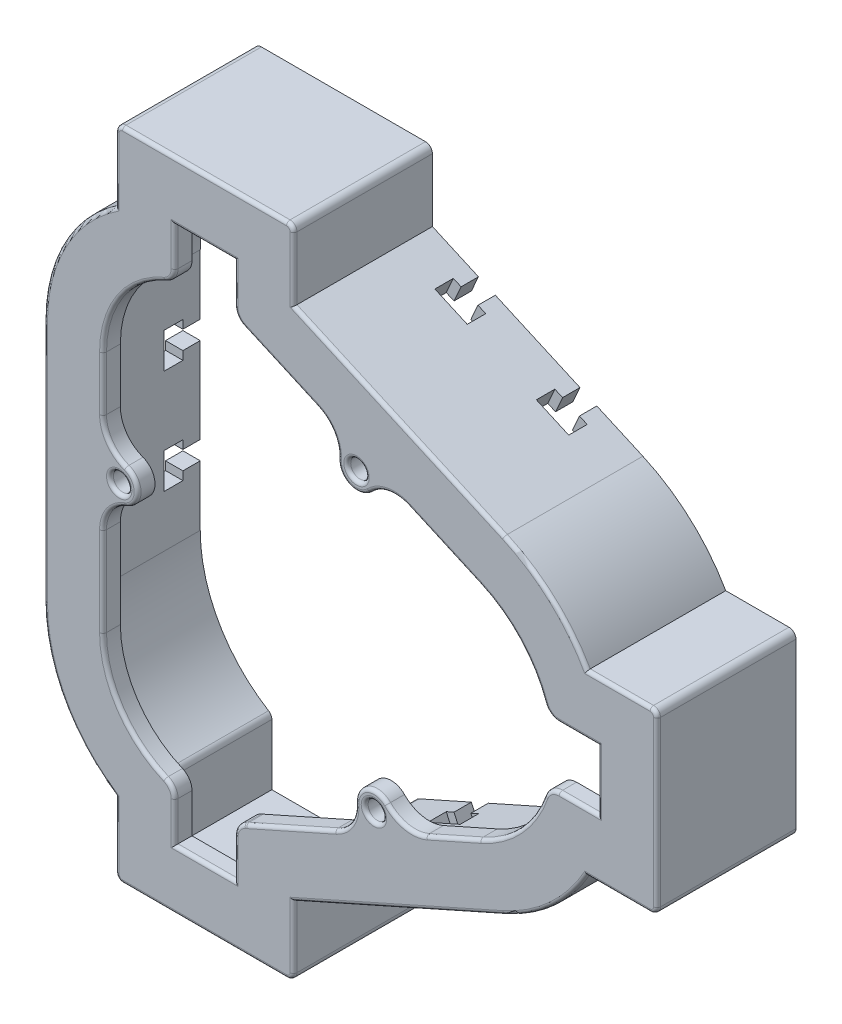
SolidWorks part; units mm, degrees
ref_plane "Front Plane" through (0, 0, 0) normal (0, 0, 1) x (1, 0, 0)
ref_plane "Top Plane" through (0, 0, 0) normal (0, 1, 0) x (1, 0, 0)
ref_plane "Right Plane" through (0, 0, 0) normal (1, 0, 0) x (0, 0, -1)
sketch "Sketch1" plane through (0, 0, -80.01) normal (0, 0, -1) x (-1, 0, 0)
  line L0 (14.1705, 137.7093) -> (22.108, 137.7093) construction
  line L1 (-128.3273, 40.8549) -> (-128.3273, 32.9174) construction
  line L2 (14.1705, -63.937) -> (22.108, -63.937) construction
  line L3 (55.2868, -7.5638) -> (55.2868, 81.3362)
  line L4 (29.093, 120.8247) -> (29.093, 135.1693)
  line L5 (29.093, 135.1693) -> (22.108, 135.1693)
  line L6 (14.1705, 135.1693) -> (22.108, 135.1693)
  line L7 (14.1705, 135.1693) -> (7.1855, 135.1693)
  line L8 (7.1855, 135.1693) -> (7.1855, 120.8247)
  line L9 (3.0278, 115.2711) -> (-82.5915, 77.144)
  line L10 (-111.5749, 47.8399) -> (-125.7873, 47.8399)
  line L11 (-125.7873, 47.8399) -> (-125.7873, 40.8549)
  line L12 (-125.7873, 40.8549) -> (-125.7873, 32.9174)
  line L13 (-125.7873, 32.9174) -> (-125.7873, 25.9324)
  line L14 (-125.7873, 25.9324) -> (-111.5749, 25.9324)
  line L15 (-82.5915, -3.3716) -> (3.0278, -41.4987)
  line L16 (7.1855, -47.0524) -> (7.1855, -61.397)
  line L17 (7.1855, -61.397) -> (14.1705, -61.397)
  line L18 (14.1705, -61.397) -> (22.108, -61.397)
  line L19 (22.108, -61.397) -> (29.093, -61.397)
  line L20 (29.093, -61.397) -> (29.093, -47.0524)
  line L21 (57.8268, -7.5638) -> (57.8268, 81.3362)
  line L22 (31.633, 120.8247) -> (31.633, 137.7093)
  line L23 (31.633, 137.7093) -> (22.108, 137.7093)
  line L24 (22.108, 137.7093) -> (22.108, 117.6323)
  line L25 (14.1705, 117.6323) -> (14.1705, 137.7093)
  line L26 (14.1705, 137.7093) -> (4.6455, 137.7093)
  line L27 (4.6455, 137.7093) -> (4.6455, 120.8247)
  line L28 (1.9945, 117.5914) -> (-83.6248, 79.4643)
  line L29 (-111.5749, 50.3799) -> (-128.3273, 50.3799)
  line L30 (-128.3273, 50.3799) -> (-128.3273, 40.8549)
  line L31 (-128.3273, 40.8549) -> (-106.0032, 40.8549)
  line L32 (-106.0032, 32.9174) -> (-128.3273, 32.9174)
  line L33 (-128.3273, 32.9174) -> (-128.3273, 23.3924)
  line L34 (-128.3273, 23.3924) -> (-111.5749, 23.3924)
  line L35 (-83.6248, -5.692) -> (1.9945, -43.8191)
  line L36 (4.6455, -47.0524) -> (4.6455, -63.937)
  line L37 (4.6455, -63.937) -> (14.1705, -63.937)
  line L38 (14.1705, -63.937) -> (14.1705, -43.86)
  line L39 (22.108, -43.86) -> (22.108, -63.937)
  line L40 (22.108, -63.937) -> (31.633, -63.937)
  line L41 (31.633, -63.937) -> (31.633, -47.0524)
  line L42 (57.8268, -7.5638) -> (57.8268, 81.3362) construction
  line L43 (31.633, 120.8247) -> (31.633, 137.7093) construction
  line L44 (31.633, 137.7093) -> (22.108, 137.7093) construction
  line L47 (14.1705, 137.7093) -> (4.6455, 137.7093) construction
  line L48 (4.6455, 137.7093) -> (4.6455, 120.8247) construction
  line L49 (1.9945, 117.5914) -> (-83.6248, 79.4643) construction
  line L50 (-111.5749, 50.3799) -> (-128.3273, 50.3799) construction
  line L51 (-128.3273, 50.3799) -> (-128.3273, 40.8549) construction
  line L54 (-128.3273, 32.9174) -> (-128.3273, 23.3924) construction
  line L55 (-128.3273, 23.3924) -> (-111.5749, 23.3924) construction
  line L56 (-83.6248, -5.692) -> (1.9945, -43.8191) construction
  line L57 (4.6455, -47.0524) -> (4.6455, -63.937) construction
  line L58 (4.6455, -63.937) -> (14.1705, -63.937) construction
  line L61 (22.108, -63.937) -> (31.633, -63.937) construction
  line L62 (31.633, -63.937) -> (31.633, -47.0524) construction
  line L63 (76.8768, -7.5638) -> (76.8768, 81.3362)
  line L64 (50.683, 130.234) -> (50.683, 156.7593)
  line L65 (50.683, 156.7593) -> (22.108, 156.7593)
  line L66 (14.1705, 156.7593) -> (22.108, 156.7593)
  line L67 (14.1705, 156.7593) -> (-14.4045, 156.7593)
  line L68 (-14.4045, 156.7593) -> (-14.4045, 131.1423)
  line L69 (-14.4045, 131.1423) -> (-91.3743, 96.8669)
  line L70 (-121.6907, 69.4299) -> (-147.3773, 69.4299)
  line L71 (-147.3773, 69.4299) -> (-147.3773, 40.8549)
  line L72 (-147.3773, 40.8549) -> (-147.3773, 32.9174)
  line L73 (-147.3773, 32.9174) -> (-147.3773, 4.3424)
  line L74 (-147.3773, 4.3424) -> (-121.6907, 4.3424)
  line L75 (-91.3743, -23.0945) -> (-14.4045, -57.3699)
  line L76 (-14.4045, -57.3699) -> (-14.4045, -82.987)
  line L77 (-14.4045, -82.987) -> (14.1705, -82.987)
  line L78 (14.1705, -82.987) -> (22.108, -82.987)
  line L79 (22.108, -82.987) -> (50.683, -82.987)
  line L80 (50.683, -82.987) -> (50.683, -56.4617)
  line L81 (70.5268, -7.5638) -> (70.5268, 81.3362)
  line L82 (44.333, 126.7051) -> (44.333, 150.4093)
  line L83 (44.333, 150.4093) -> (22.108, 150.4093)
  line L84 (14.1705, 150.4093) -> (22.108, 150.4093)
  line L85 (14.1705, 150.4093) -> (-8.0545, 150.4093)
  line L86 (-8.0545, 150.4093) -> (-8.0545, 127.0188)
  line L87 (-8.0545, 127.0188) -> (-88.7911, 91.066)
  line L88 (-117.8756, 63.0799) -> (-141.0273, 63.0799)
  line L89 (-141.0273, 63.0799) -> (-141.0273, 40.8549)
  line L90 (-141.0273, 40.8549) -> (-141.0273, 32.9174)
  line L91 (-141.0273, 32.9174) -> (-141.0273, 10.6924)
  line L92 (-141.0273, 10.6924) -> (-117.8756, 10.6924)
  line L93 (-88.7911, -17.2937) -> (-8.0545, -53.2465)
  line L94 (-8.0545, -53.2465) -> (-8.0545, -76.637)
  line L95 (-8.0545, -76.637) -> (14.1705, -76.637)
  line L96 (14.1705, -76.637) -> (22.108, -76.637)
  line L97 (22.108, -76.637) -> (44.333, -76.637)
  line L98 (44.333, -76.637) -> (44.333, -52.9327)
  circle A3 centre (18.1393, 81.3362) radius 19.05 construction
  circle A4 centre (18.1393, -7.5638) radius 47.625 construction
  circle A5 centre (-58.3701, 37.7264) radius 19.05 construction
  arc A6 (-37.3265, 52.1691) -> (-96.2173, 33.5834) centre (-66.7719, 42.8762) ccw construction
  arc A7 (-37.3265, 52.1691) -> (-96.2173, 33.5834) centre (-66.7719, 42.8762) ccw construction
  arc A8 (-97.1709, 33.2824) -> (-36.3728, 52.4701) centre (-66.7719, 42.8762) ccw construction
  arc A9 (-97.1709, 33.2824) -> (-36.3728, 52.4701) centre (-66.7719, 42.8762) ccw construction
  circle A10 centre (18.1393, 81.3362) radius 36.5125 construction
  circle A11 centre (18.1393, 81.3362) radius 36.5125 construction
  circle A12 centre (49.3813, 43.2476) radius 3.3782
  circle A13 centre (-43.805, -14.1791) radius 3.3782
  circle A14 centre (-37.4305, 90.7903) radius 3.3782
  arc A15 (33.5733, -44.1273) -> (57.8268, -7.5638) centre (18.1393, -7.5638) ccw
  arc A16 (57.8268, 81.3362) -> (33.5733, 117.8997) centre (18.1393, 81.3362) ccw
  arc A17 (31.633, 120.8247) -> (33.5733, 117.8997) centre (34.808, 120.8247) ccw
  arc A18 (14.1705, 117.6323) -> (22.108, 117.6323) centre (18.1393, 81.3362) ccw
  arc A19 (2.7053, 117.8997) -> (4.6455, 120.8247) centre (1.4705, 120.8247) ccw
  arc A20 (2.7053, 117.8997) -> (1.9945, 117.5914) centre (18.1393, 81.3362) ccw
  arc A21 (-83.6248, 79.4643) -> (-108.5831, 52.4919) centre (-64.6643, 36.8862) ccw
  arc A22 (-111.5749, 50.3799) -> (-108.5831, 52.4919) centre (-111.5749, 53.5549) ccw
  arc A23 (-106.0032, 32.9174) -> (-106.0032, 40.8549) centre (-64.6643, 36.8862) ccw
  arc A24 (-108.5831, 21.2805) -> (-111.5749, 23.3924) centre (-111.5749, 20.2174) ccw
  arc A25 (-108.5831, 21.2805) -> (-83.6248, -5.692) centre (-64.6643, 36.8862) ccw
  arc A26 (1.9945, -43.8191) -> (2.7053, -44.1273) centre (18.1393, -7.5638) ccw
  arc A27 (4.6455, -47.0524) -> (2.7053, -44.1273) centre (1.4705, -47.0524) ccw
  arc A28 (22.108, -43.86) -> (14.1705, -43.86) centre (18.1393, -7.5638) ccw
  arc A29 (33.5733, -44.1273) -> (31.633, -47.0524) centre (34.808, -47.0524) ccw
  arc A30 (33.5733, -44.1273) -> (57.8268, -7.5638) centre (18.1393, -7.5638) ccw construction
  arc A31 (57.8268, 81.3362) -> (33.5733, 117.8997) centre (18.1393, 81.3362) ccw construction
  arc A32 (31.633, 120.8247) -> (33.5733, 117.8997) centre (34.808, 120.8247) ccw construction
  arc A34 (2.7053, 117.8997) -> (4.6455, 120.8247) centre (1.4705, 120.8247) ccw construction
  arc A35 (2.7053, 117.8997) -> (1.9945, 117.5914) centre (18.1393, 81.3362) ccw construction
  arc A36 (-83.6248, 79.4643) -> (-108.5831, 52.4919) centre (-64.6643, 36.8862) ccw construction
  arc A37 (-111.5749, 50.3799) -> (-108.5831, 52.4919) centre (-111.5749, 53.5549) ccw construction
  arc A39 (-108.5831, 21.2805) -> (-111.5749, 23.3924) centre (-111.5749, 20.2174) ccw construction
  arc A40 (-108.5831, 21.2805) -> (-83.6248, -5.692) centre (-64.6643, 36.8862) ccw construction
  arc A41 (1.9945, -43.8191) -> (2.7053, -44.1273) centre (18.1393, -7.5638) ccw construction
  arc A42 (4.6455, -47.0524) -> (2.7053, -44.1273) centre (1.4705, -47.0524) ccw construction
  arc A44 (33.5733, -44.1273) -> (31.633, -47.0524) centre (34.808, -47.0524) ccw construction
  arc A45 (-80.8179, 75.1448) -> (-76.0259, 76.8308) centre (-64.6643, 36.8862) ccw construction
  arc A46 (-80.8179, 75.1448) -> (-76.0259, 76.8308) centre (-64.6643, 36.8862) ccw construction
  circle A47 centre (-43.805, -14.1791) radius 6.7564
  circle A48 centre (49.3813, 43.2476) radius 6.7564
  circle A49 centre (-37.4305, 90.7903) radius 6.7564
  arc A50 (32.5855, -41.7872) -> (55.2868, -7.5638) centre (18.1393, -7.5638) ccw
  arc A51 (55.2868, 81.3362) -> (32.5855, 115.5596) centre (18.1393, 81.3362) ccw
  arc A52 (29.093, 120.8247) -> (32.5855, 115.5596) centre (34.808, 120.8247) ccw
  arc A53 (3.693, 115.5596) -> (7.1855, 120.8247) centre (1.4705, 120.8247) ccw
  arc A54 (3.693, 115.5596) -> (3.0278, 115.2711) centre (18.1393, 81.3362) ccw
  arc A55 (-82.5915, 77.144) -> (-106.1897, 51.6414) centre (-64.6643, 36.8862) ccw
  arc A56 (-111.5749, 47.8399) -> (-106.1897, 51.6414) centre (-111.5749, 53.5549) ccw
  arc A57 (-106.1897, 22.1309) -> (-111.5749, 25.9324) centre (-111.5749, 20.2174) ccw
  arc A58 (-106.1897, 22.1309) -> (-82.5915, -3.3716) centre (-64.6643, 36.8862) ccw
  arc A59 (3.0278, -41.4987) -> (3.693, -41.7872) centre (18.1393, -7.5638) ccw
  arc A60 (7.1855, -47.0524) -> (3.693, -41.7872) centre (1.4705, -47.0524) ccw
  arc A61 (32.5855, -41.7872) -> (29.093, -47.0524) centre (34.808, -47.0524) ccw
  arc A62 (50.683, -56.4617) -> (76.8768, -7.5638) centre (18.1393, -7.5638) ccw
  arc A63 (76.8768, 81.3362) -> (50.683, 130.234) centre (18.1393, 81.3362) ccw
  arc A64 (50.683, 130.234) -> (50.683, 130.234) centre (50.683, 130.234) ccw
  arc A65 (-14.4045, 131.1423) -> (-14.4045, 131.1423) centre (-14.4045, 131.1423) ccw
  arc A66 (-14.4045, 131.1423) -> (-14.4045, 131.1423) centre (-14.4045, 131.1423) cw
  arc A67 (-91.3743, 96.8669) -> (-121.6907, 69.4299) centre (-64.6643, 36.8862) ccw
  arc A68 (-121.6907, 69.4299) -> (-121.6907, 69.4299) centre (-121.6907, 69.4299) ccw
  arc A69 (-121.6907, 4.3424) -> (-121.6907, 4.3424) centre (-121.6907, 4.3424) ccw
  arc A70 (-121.6907, 4.3424) -> (-91.3743, -23.0945) centre (-64.6643, 36.8862) ccw
  arc A71 (-14.4045, -57.3699) -> (-14.4045, -57.3699) centre (-14.4045, -57.3699) cw
  arc A72 (-14.4045, -57.3699) -> (-14.4045, -57.3699) centre (-14.4045, -57.3699) ccw
  arc A73 (50.683, -56.4617) -> (50.683, -56.4617) centre (50.683, -56.4617) ccw
  arc A74 (44.333, -52.9327) -> (70.5268, -7.5638) centre (18.1393, -7.5638) ccw
  arc A75 (70.5268, 81.3362) -> (44.333, 126.7051) centre (18.1393, 81.3362) ccw
  arc A76 (44.333, 126.7051) -> (44.333, 126.7051) centre (44.333, 126.7051) ccw
  arc A77 (-8.0545, 127.0188) -> (-8.0545, 127.0188) centre (-8.0545, 127.0188) ccw
  arc A78 (-8.0545, 127.0188) -> (-8.0545, 127.0188) centre (-8.0545, 127.0188) cw
  arc A79 (-88.7911, 91.066) -> (-117.8756, 63.0799) centre (-64.6643, 36.8862) ccw
  arc A80 (-117.8756, 63.0799) -> (-117.8756, 63.0799) centre (-117.8756, 63.0799) ccw
  arc A81 (-117.8756, 10.6924) -> (-117.8756, 10.6924) centre (-117.8756, 10.6924) ccw
  arc A82 (-117.8756, 10.6924) -> (-88.7911, -17.2937) centre (-64.6643, 36.8862) ccw
  arc A83 (-8.0545, -53.2465) -> (-8.0545, -53.2465) centre (-8.0545, -53.2465) cw
  arc A84 (-8.0545, -53.2465) -> (-8.0545, -53.2465) centre (-8.0545, -53.2465) ccw
  arc A85 (44.333, -52.9327) -> (44.333, -52.9327) centre (44.333, -52.9327) ccw
  point P68 (-40.8151, 98.5279)
  arc M83 (33.5733, -44.1273) -> (57.8268, -7.5638) centre (18.1393, -7.5638) ccw
  line M84 (57.8268, -7.5638) -> (57.8268, 81.3362)
  arc M85 (57.8268, 81.3362) -> (33.5733, 117.8997) centre (18.1393, 81.3362) ccw
  arc M86 (33.5733, 117.8997) -> (31.633, 120.8247) centre (34.808, 120.8247) cw
  line M87 (31.633, 120.8247) -> (31.633, 137.7093)
  line M88 (31.633, 137.7093) -> (22.108, 137.7093)
  line M89 (22.108, 137.7093) -> (22.108, 117.6323)
  line M91 (14.1705, 117.6323) -> (14.1705, 137.7093)
  line M92 (14.1705, 137.7093) -> (4.6455, 137.7093)
  line M93 (4.6455, 137.7093) -> (4.6455, 120.8247)
  arc M94 (4.6455, 120.8247) -> (2.7053, 117.8997) centre (1.4705, 120.8247) cw
  arc M95 (2.7053, 117.8997) -> (1.9945, 117.5914) centre (18.1393, 81.3362) ccw
  line M96 (1.9945, 117.5914) -> (-83.6248, 79.4643)
  arc M97 (-83.6248, 79.4643) -> (-108.5831, 52.4919) centre (-64.6643, 36.8862) ccw
  arc M98 (-108.5831, 52.4919) -> (-111.5749, 50.3799) centre (-111.5749, 53.5549) cw
  line M99 (-111.5749, 50.3799) -> (-128.3273, 50.3799)
  line M100 (-128.3273, 50.3799) -> (-128.3273, 40.8549)
  line M101 (-128.3273, 40.8549) -> (-106.0032, 40.8549)
  line M103 (-106.0032, 32.9174) -> (-128.3273, 32.9174)
  line M104 (-128.3273, 32.9174) -> (-128.3273, 23.3924)
  line M105 (-128.3273, 23.3924) -> (-111.5749, 23.3924)
  arc M106 (-111.5749, 23.3924) -> (-108.5831, 21.2805) centre (-111.5749, 20.2174) cw
  arc M107 (-108.5831, 21.2805) -> (-83.6248, -5.692) centre (-64.6643, 36.8862) ccw
  line M108 (-83.6248, -5.692) -> (1.9945, -43.8191)
  arc M109 (1.9945, -43.8191) -> (2.7053, -44.1273) centre (18.1393, -7.5638) ccw
  arc M110 (2.7053, -44.1273) -> (4.6455, -47.0524) centre (1.4705, -47.0524) cw
  line M111 (4.6455, -47.0524) -> (4.6455, -63.937)
  line M112 (4.6455, -63.937) -> (14.1705, -63.937)
  line M113 (14.1705, -63.937) -> (14.1705, -43.86)
  line M115 (22.108, -43.86) -> (22.108, -63.937)
  line M116 (22.108, -63.937) -> (31.633, -63.937)
  line M117 (31.633, -63.937) -> (31.633, -47.0524)
  arc M118 (31.633, -47.0524) -> (33.5733, -44.1273) centre (34.808, -47.0524) cw
  dimension "D2" = 6.7564
  dimension "D3" = 8.4455
  dimension "D4" = 8.4455
  dimension "D5" = 8.4455
  dimension "D6" = 3.3782
  dimension "D1" = 0
  dimension "D7" = 2.54
  dimension "D8" = 19.05
  dimension "D9" = 12.7
extrude "Boss-Extrude1" add sketch "Sketch1" along normal blind 6.35 contours L3 A48 A12 | L9 A49 A14 | L15 A47 A13 | L92 A82 L93 L94 L95 L96 L97 L98 A74 L81 A75 L82 L83 L84 L85 L86 L87 A79 L88 L89 L90 L91 L18 L12 L6 M113 M112 M111 M110 M109 M108 M107 M106 M105 M104 M103 M101 M100 M99 M98 M97 M96 M95 M94 M93 M92 M91 M89 M88 M87 | L16 A60 A59 L15 A47 A58 A57 L14 L13 L17 M103 M104 M105 M106 M107 M108 M109 M110 M111 M112 M113 | A50 A61 L20 L19 L5 L4 A52 A51 L3 A48 M115 M116 M117 M118 M83 M84 M85 M86 M87 M88 M89 | L10 A56 A55 L9 A49 A54 A53 L8 L7 L11 M91 M92 M93 M94 M95 M96 M97 M98 M99 M100 M101 | L74 A70 L75 L76 L77 L78 L79 L80 A62 L63 A63 L64 L65 L66 L67 L68 L69 A67 L70 L71 L72 L73 A82 L92 L91 L90 L89 L88 A79 L87 L86 L85 L84 L83 L82 A75 L81 A74 L98 L97 L96 L95 L94 L93 | L3 A48 | L9 A49 | L15 A47 region at (-57.3347, 16.2007, -80.01) region at (-42.8101, 43.2476, -80.01) region at (-55.6291, 43.2476, -80.01) region at (-12.4476, -62.667, -80.01) region at (-10.678, 136.8923, -80.01) region at (46.3466, -19.8865, -80.01) region at (46.1297, -19.3994, -80.01) region at (32.5874, 95.2231, -80.01) region at (39.972, 96.4976, -80.01) region at (-67.0221, -33.7495, -80.01) region at (-60.8207, -32.2059, -80.01)
extrude "Boss-Extrude2" add sketch "Sketch1<3>" along normal blind 50.8 contours L74 A70 L75 L76 L77 L78 L79 L80 A62 L63 A63 L64 L65 L66 L67 L68 L69 A67 L70 L71 L72 L73 A82 L92 L91 L90 L89 L88 A79 L87 L86 L85 L84 L83 L82 A75 L81 A74 L98 L97 L96 L95 L94 L93 region at (-67.0221, -33.7495, -80.01)
sketch "Sketch1<3>" plane through (0, 0, -80.01) normal (0, 0, -1) x (-1, 0, 0) same geometry as "Sketch1"
sketch "Sketch2" plane through (-76.8768, 0, 0) normal (-1, 0, 0) x (0, 0, 1)
  line L0 (-80.01, 36.8862) -> (-130.81, 36.8862) construction
  line L1 (-130.81, 395.458) -> (-130.81, 402.2144)
  line L2 (-80.01, -7.5638) -> (-80.01, 81.3362) construction
  line L3 (-130.81, -7.5638) -> (-130.81, 81.3362) construction
  line L4 (-130.81, 52.558) -> (-124.46, 52.558)
  line L5 (-124.46, 52.558) -> (-124.46, 49.4592)
  line L6 (-124.46, 49.4592) -> (-117.602, 49.4592)
  line L7 (-117.602, 49.4592) -> (-117.602, 62.4132)
  line L8 (-117.602, 55.9362) -> (-130.81, 55.9362) construction
  line L9 (-124.46, 62.4132) -> (-117.602, 62.4132)
  line L10 (-130.81, 59.3144) -> (-124.46, 59.3144)
  line L11 (-124.46, 59.3144) -> (-124.46, 62.4132)
  line L12 (-130.81, 14.458) -> (-124.46, 14.458)
  line L13 (-124.46, 14.458) -> (-124.46, 11.3592)
  line L14 (-124.46, 11.3592) -> (-117.602, 11.3592)
  line L15 (-117.602, 24.3132) -> (-117.602, 11.3592)
  line L16 (-124.46, 24.3132) -> (-117.602, 24.3132)
  line L17 (-124.46, 21.2144) -> (-124.46, 24.3132)
  line L18 (-130.81, 21.2144) -> (-124.46, 21.2144)
  line L19 (-130.81, 14.458) -> (-130.81, 21.2144)
  line L20 (-130.81, 52.558) -> (-130.81, 59.3144)
  line L21 (-130.81, 402.2144) -> (-124.46, 402.2144)
  line L22 (-124.46, 402.2144) -> (-124.46, 405.3132)
  line L23 (-124.46, 405.3132) -> (-117.602, 405.3132)
  line L24 (-117.602, 405.3132) -> (-117.602, 392.3592)
  line L25 (-124.46, 392.3592) -> (-117.602, 392.3592)
  line L26 (-124.46, 395.458) -> (-124.46, 392.3592)
  line L27 (-130.81, 395.458) -> (-124.46, 395.458)
  line L28 (-130.81, 433.558) -> (-130.81, 440.3144)
  line L29 (-130.81, 440.3144) -> (-124.46, 440.3144)
  line L30 (-124.46, 440.3144) -> (-124.46, 443.4132)
  line L31 (-124.46, 443.4132) -> (-117.602, 443.4132)
  line L32 (-117.602, 430.4592) -> (-117.602, 443.4132)
  line L33 (-124.46, 430.4592) -> (-117.602, 430.4592)
  line L34 (-124.46, 433.558) -> (-124.46, 430.4592)
  line L35 (-130.81, 433.558) -> (-124.46, 433.558)
  dimension "D1" = 6.858
  dimension "D2" = 6.7564
  dimension "D3" = 6.35
  dimension "D4" = 19.05
  dimension "D6" = 6.477
  dimension "D5" = 2
sketch "Sketch3" plane through (51.1185, 114.7931, 0) normal (0.4068, 0.9135, 0) x (0.9135, -0.4068, 0)
  line L0 (1.9385, 130.81) -> (1.9385, 80.01) construction
  line L1 (-40.1897, 130.81) -> (44.0668, 130.81) construction
  line L2 (-40.1897, 80.01) -> (44.0668, 80.01) construction
  line L3 (22.2585, 130.81) -> (22.2585, 117.7036) construction
  line L4 (18.8803, 130.81) -> (18.8803, 124.46)
  line L5 (18.8803, 124.46) -> (15.7815, 124.46)
  line L6 (15.7815, 124.46) -> (15.7815, 117.7036)
  line L7 (15.7815, 117.7036) -> (28.7355, 117.7036)
  line L8 (28.7355, 124.46) -> (28.7355, 117.7036)
  line L9 (25.6367, 124.46) -> (28.7355, 124.46)
  line L10 (25.6367, 130.81) -> (25.6367, 124.46)
  line L11 (-18.3815, 130.81) -> (-18.3815, 117.7036) construction
  line L12 (-21.7597, 130.81) -> (-21.7597, 124.46)
  line L13 (-15.0033, 130.81) -> (-15.0033, 124.46)
  line L14 (-21.7597, 124.46) -> (-24.8585, 124.46)
  line L15 (-24.8585, 124.46) -> (-24.8585, 117.7036)
  line L16 (-15.0033, 124.46) -> (-11.9045, 124.46)
  line L17 (-11.9045, 124.46) -> (-11.9045, 117.7036)
  line L18 (-11.9045, 117.7036) -> (-24.8585, 117.7036)
  line L19 (-21.7597, 130.81) -> (-15.0033, 130.81)
  line L20 (18.8803, 130.81) -> (25.6367, 130.81)
  dimension "D1" = 3.3782
  dimension "D2" = 6.7564
  dimension "D3" = 6.35
  dimension "D4" = 6.477
  dimension "D5" = 20.32
extrude "Cut-Extrude1" cut sketch "Sketch3" against normal blind 18.542
ref_plane "Plane4" through (0, 36.8862, 0) normal (0, 1, 0) x (1, 0, 0)
mirror "Mirror1" about plane through (0, 36.8862, 0) normal (0, 1, 0) of "Cut-Extrude1"
extrude "Cut-Extrude2" cut sketch "Sketch2" against normal blind 18.542
fillet "Fillet1" radius 12.7 6 edges at (49.2059, -18.2386, -83.185) (43.2089, -20.9091, -83.185) (-55.2868, 46.53, -83.185) (-55.2868, 39.9652, -83.185) (42.8316, 94.8495, -83.185) (36.8339, 97.5203, -83.185)
fillet "Fillet2" radius 2.54 16 edges at (141.0273, 63.0799, -108.585) (141.0273, 10.6924, -108.585) (8.0545, 150.4093, -108.585) (-44.333, 150.4093, -108.585) (8.0545, 127.0188, -108.585) (-44.333, 126.7051, -108.585) (8.0545, -53.2465, -108.585) (-44.333, -52.9327, -108.585) (14.4045, -82.987, -105.41) (-50.683, -82.987, -105.41) (-50.683, 156.7593, -105.41) (14.4045, 156.7593, -105.41) (147.3773, 69.4299, -105.41) (147.3773, 4.3424, -105.41) (117.8756, 10.6924, -108.585) (117.8756, 63.0799, -108.585)
fillet "Fillet3" radius 1.27 61 edges at (-49.9391, -82.243, -80.01) (-50.683, -68.4543, -80.01) (-69.9159, -35.2997, -80.01) (-76.8768, 36.8862, -80.01) (-69.9159, 109.072, -80.01) (-50.683, 142.2267, -80.01) (-49.9391, 156.0154, -80.01) (-18.1393, 156.7593, -80.01) (13.6605, 156.0154, -80.01) (14.4045, 142.6808, -80.01) (52.8894, 114.0046, -80.01) (108.7227, 85.5684, -80.01) (133.264, 69.4299, -80.01) (146.6333, 68.686, -80.01) (147.3773, 36.8862, -80.01) (146.6333, 5.0864, -80.01) (133.264, 4.3424, -80.01) (108.7227, -11.7961, -80.01) (52.8894, -40.2322, -80.01) (14.4045, -68.9084, -80.01) (13.6605, -82.243, -80.01) (-18.1393, -82.987, -80.01) (34.0523, 90.7903, -80.01) (-52.7595, 43.2476, -80.01) (40.4268, -14.1791, -80.01) (118.6811, 47.8399, -80.01) (108.279, 48.886, -80.01) (97.0101, 66.8166, -80.01) (69.5395, 82.9562, -80.01) (48.9466, 89.6427, -80.01) (34.682, 84.6182, -80.01) (28.873, 98.5817, -80.01) (10.0751, 109.4362, -80.01) (-3.3597, 115.417, -80.01) (-6.233, 117.6657, -80.01) (-7.1855, 127.997, -80.01) (-18.1393, 135.1693, -80.01) (-29.093, 127.997, -80.01) (-30.0455, 117.6657, -80.01) (-49.0955, 101.8702, -80.01) (-55.2868, 71.4076, -80.01) (-53.0179, 54.2346, -80.01) (-42.6249, 43.2476, -80.01) (-53.0179, 32.2606, -80.01) (-55.2868, 8.7262, -80.01) (-49.0955, -28.0979, -80.01) (-30.0455, -43.8933, -80.01) (-29.093, -54.2247, -80.01) (-18.1393, -61.397, -80.01) (-7.1855, -54.2247, -80.01) (-6.233, -43.8933, -80.01) (-3.3597, -41.6446, -80.01) (13.2624, -34.2446, -80.01) (35.2476, -21.9706, -80.01) (41.0565, -8.007, -80.01) (55.3212, -13.0317, -80.01) (72.7268, -7.7645, -80.01) (97.0101, 6.9558, -80.01) (108.279, 24.8863, -80.01) (118.6811, 25.9324, -80.01) (125.7873, 36.8862, -80.01)
equation "\"D4@Sketch1\"=\"D3@Sketch1\""
equation "\"D5@Sketch1\"=\"D3@Sketch1\""
